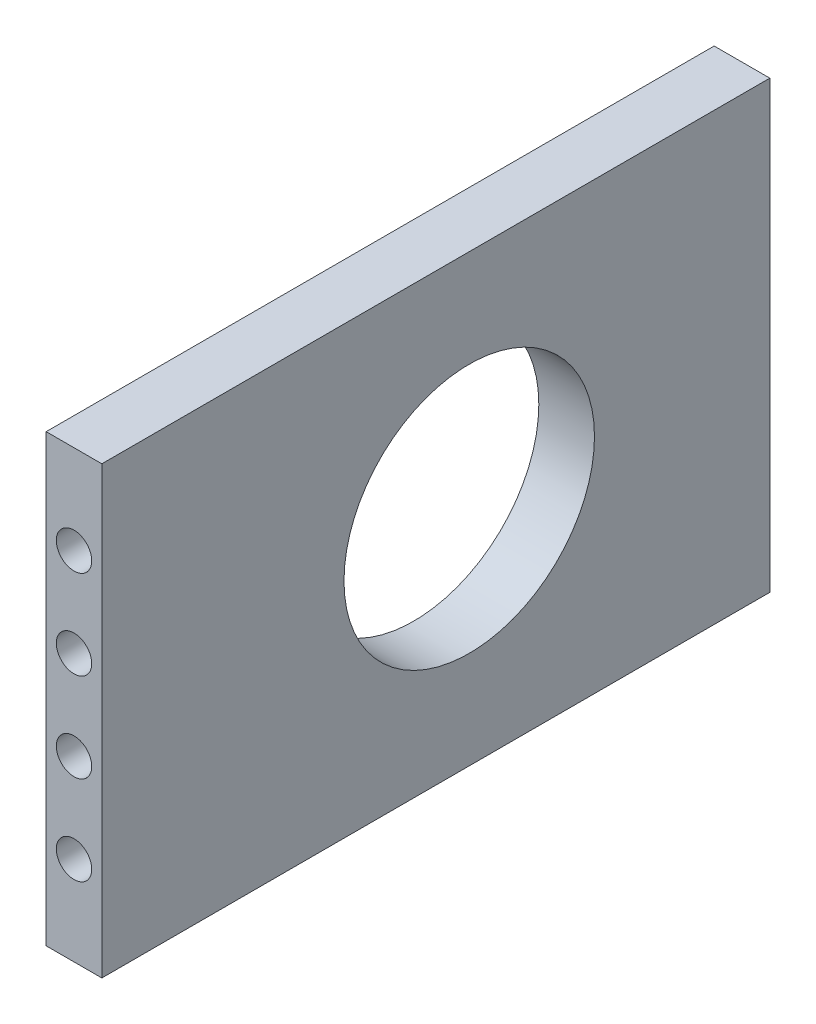
SolidWorks part; units mm, degrees
material "6061-T6 (SS)"
ref_plane "Front" through (0, 0, 0) normal (0, 0, 1) x (1, 0, 0)
ref_plane "Top" through (0, 0, 0) normal (0, 1, 0) x (1, 0, 0)
ref_plane "Right" through (0, 0, 0) normal (1, 0, 0) x (0, 0, -1)
sketch "Sketch2" plane through (0, 0, 0) normal (1, 0, 0) x (0, 0, -1)
  line L1 (-38.1, -25.4) -> (38.1, -25.4)
  line L2 (-38.1, -25.4) -> (-38.1, 25.4)
  line L3 (-38.1, 25.4) -> (38.1, 25.4)
  line L4 (38.1, -25.4) -> (38.1, 25.4)
  line L5 (-38.1, -25.4) -> (38.1, 25.4) construction
  line L6 (-38.1, 25.4) -> (38.1, -25.4) construction
  point P0 (0, 0)
  dimension "D1" = 76.2
  dimension "D2" = 50.8
extrude "Boss-Extrude2" add sketch "Sketch2" along normal blind 6.35
hole_wizard "#10-32 Tapped Hole1" positions "Sketch3" profile "Sketch5" tap size "#10-32" standard "ANSI Inch"
sketch "Sketch3" plane through (0, 0, 38.1) normal (0, 0, 1) x (1, 0, 0)
  line L0 (3.175, 25.4) -> (3.175, 15.24) construction
  line L1 (6.35, 25.4) -> (0, 25.4) construction
  line L2 (3.175, 15.24) -> (3.175, 5.08) construction
  line L3 (3.175, 5.08) -> (3.175, -5.08) construction
  line L4 (3.175, -5.08) -> (3.175, -15.24) construction
  line L5 (3.175, -15.24) -> (3.175, -25.4) construction
  line L6 (6.35, -25.4) -> (0, -25.4) construction
  point P0 (3.175, -15.24)
  point P2 (3.175, -5.08)
  point P4 (3.175, 5.08)
  point P6 (3.175, 15.24)
sketch "Sketch5" plane through (3.175, -15.24, 38.1) normal (1, 0, 0) x (0, -1, 0)
  line L0 (0, 0) -> (0, 26.6133)
  line L1 (0, 26.6133) -> (2.0193, 25.4)
  line L2 (2.0193, 25.4) -> (2.0193, 0)
  line L5 (2.0193, 0) -> (0, 0)
  line L10 (0, 26.6133) -> (-2.0193, 25.4) construction
  line L11 (0, -6.35) -> (0, 107.95) construction
  dimension "Tap Drill Dia." = 4.0386
  dimension "Tap Drill Depth" = 25.4
  dimension "Drill Angle" = 118
cosmetic thread "Hole Thread1" parameters "D1"=9.652, "D2"=4.826
cosmetic thread "Hole Thread2" parameters "D1"=9.652, "D2"=4.826
cosmetic thread "Hole Thread3" parameters "D1"=9.652, "D2"=4.826
cosmetic thread "Hole Thread4" parameters "D1"=9.652, "D2"=4.826
sketch "Sketch6" plane through (6.35, 0, 0) normal (1, 0, 0) x (0, 0, -1)
  line L0 (-38.1, 25.4) -> (-38.1, -25.4) construction
  line L1 (-38.1, -25.4) -> (38.1, -25.4) construction
  circle A0 centre (3.81, 0) radius 14.2875
  dimension "D1" = 41.91
  dimension "D3" = 28.575
  dimension "D2" = 25.4
extrude "Cut-Extrude1" cut sketch "Sketch6" against normal through all
